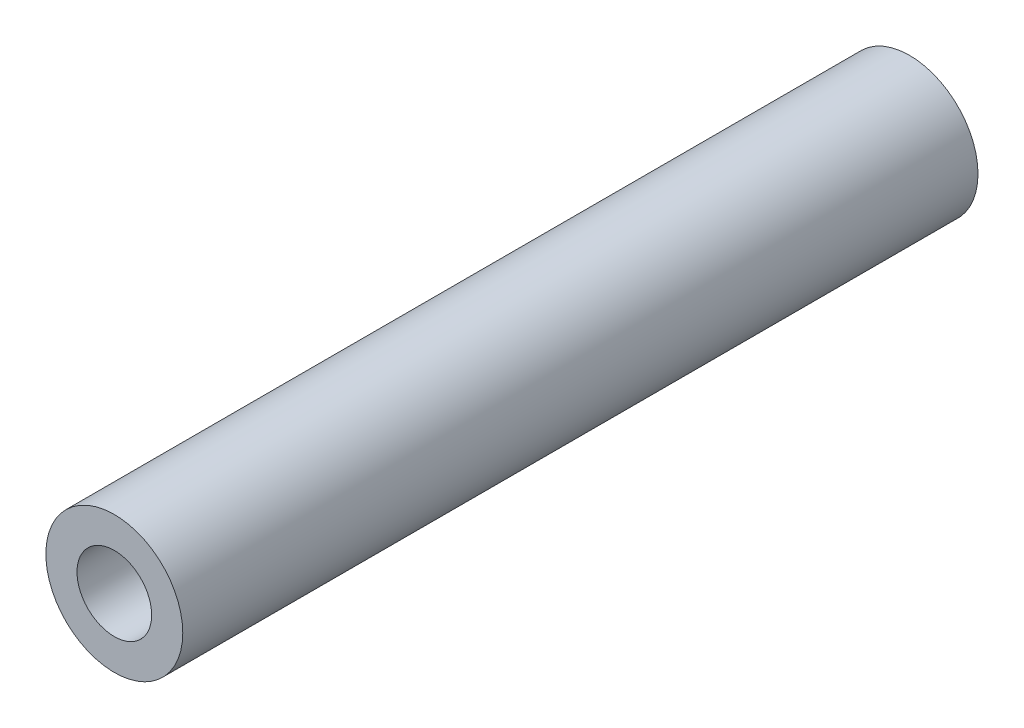
SolidWorks part; units mm, degrees
ref_plane "Front Plane" through (0, 0, 0) normal (0, 0, 1) x (1, 0, 0)
ref_plane "Top Plane" through (0, 0, 0) normal (0, 1, 0) x (1, 0, 0)
ref_plane "Right Plane" through (0, 0, 0) normal (1, 0, 0) x (0, 0, -1)
sketch "Sketch1" plane through (0, 0, 0) normal (0, 0, 1) x (1, 0, 0)
  circle A0 centre (0, 0) radius 1.5
  circle A1 centre (0, 0) radius 2.75
  dimension "D1" = 3
  dimension "D2" = 5.5
extrude "Boss-Extrude1" add sketch "Sketch1" along normal blind 31.95
